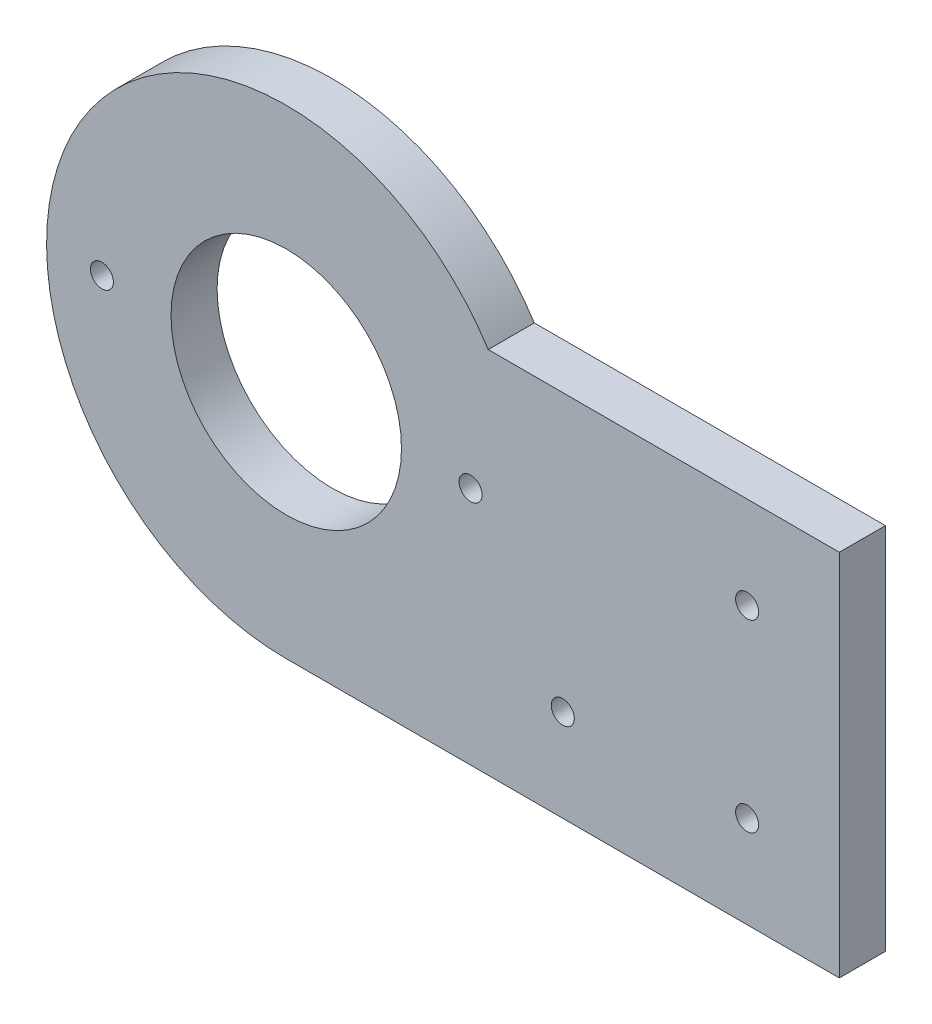
SolidWorks part; units mm, degrees
ref_plane "Front Plane" through (0, 0, 0) normal (0, 0, 1) x (1, 0, 0)
ref_plane "Top Plane" through (0, 0, 0) normal (0, 1, 0) x (1, 0, 0)
ref_plane "Right Plane" through (0, 0, 0) normal (1, 0, 0) x (0, 0, -1)
sketch "Sketch1" plane through (0, 0, 0) normal (0, 0, 1) x (1, 0, 0)
  line L0 (0, -33.02) -> (76.2, -33.02)
  line L1 (76.2, -33.02) -> (76.2, -7.62)
  line L2 (76.2, -7.62) -> (32.1287, -7.62)
  line L3 (25.4, 0) -> (-25.4, 0) construction
  line L4 (76.2, -20.32) -> (32.1287, -20.32) construction
  line L5 (32.1287, -20.32) -> (32.1287, -7.62) construction
  arc A0 (0, -33.02) -> (32.1287, -7.62) centre (0, 0) cw
  circle A1 centre (0, 0) radius 15.875
  circle A2 centre (-25.4, 0) radius 1.5875
  circle A3 centre (25.4, 0) radius 1.5875
  circle A4 centre (38.1, -20.32) radius 1.5875
  circle A5 centre (63.5, -20.32) radius 1.5875
  point P13 (0, 0)
  dimension "D1" = 33.02
  dimension "D4" = 31.75
  dimension "D5" = 3.175
  dimension "D7" = 3.175
  dimension "D2" = 25.4
  dimension "D3" = 76.2
  dimension "D6" = 50.8
  dimension "D8" = 12.7
  dimension "D9" = 25.4
extrude "Boss-Extrude1" add sketch "Sketch1" along normal blind 6.35
sketch "Sketch2" plane through (0, 0, 6.35) normal (0, 0, 1) x (1, 0, 0)
  line L0 (76.2, -7.62) -> (76.2, 17.78)
  line L1 (76.2, 17.78) -> (27.8243, 17.78)
  line L4 (76.2, -7.62) -> (32.1287, -7.62) construction
  line L5 (32.1287, -7.62) -> (76.2, -7.62)
  line L6 (76.2, 5.08) -> (32.6269, 5.08) construction
  arc A0 (32.1287, -7.62) -> (0, -33.02) centre (0, 0) ccw construction
  arc A1 (27.8243, 17.78) -> (32.1287, -7.62) centre (0, 0) cw
  circle A2 centre (63.5, 5.08) radius 1.5875
  circle A5 centre (63.5, -20.32) radius 1.5875 construction
  dimension "D1" = 25.4
  dimension "D2" = 12.7
extrude "Boss-Extrude2" add sketch "Sketch2" against normal up to surface (6.35 mm away) up to face at (39.6875, -20.32, 0)
